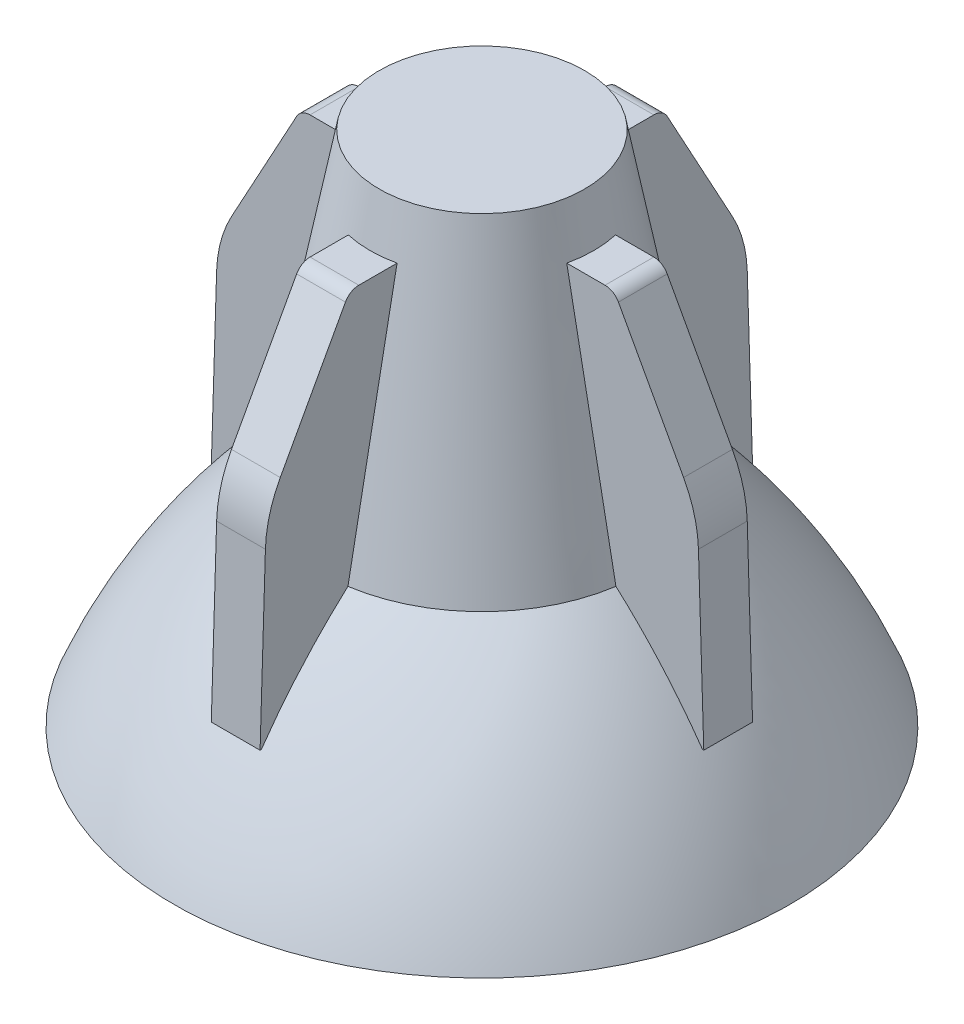
SolidWorks part; units mm, degrees
ref_plane "Front Plane" through (0, 0, 0) normal (0, 0, 1) x (1, 0, 0)
ref_plane "Top Plane" through (0, 0, 0) normal (0, 1, 0) x (1, 0, 0)
ref_plane "Right Plane" through (0, 0, 0) normal (1, 0, 0) x (0, 0, -1)
sketch "Sketch1" plane through (0, 0, 0) normal (0, 0, 1) x (1, 0, 0)
  line L0 (433.5511, 624.0548) -> (524.1181, 578.0747)
  line L1 (533.0823, 575.4497) -> (710.8345, 557.6264)
  line L2 (710.8345, 547.4101) -> (526.2364, 547.4101)
  line L3 (526.2364, 547.4101) -> (431.0532, 619.1347)
  arc A0 (524.1181, 578.0747) -> (533.0823, 575.4497) centre (535.6165, 600.723) ccw
  arc A1 (710.8345, 547.4101) -> (710.8345, 557.6264) centre (710.8345, 552.5182) ccw
  arc A2 (433.5511, 624.0548) -> (431.0532, 619.1347) centre (432.3022, 621.5948) ccw
  dimension "D1" = 25.4
extrude "Extrude1" [suppressed] add sketch "Sketch1" against normal blind 177.8
ref_plane "Plane1" [suppressed] through (62.433, 622.6422, 0) normal (0.0998, 0.995, 0) x (-0.995, 0.0998, 0)
sketch "Sketch5" [suppressed] plane through (62.433, 622.6422, 0) normal (0.0998, 0.995, 0) x (-0.995, 0.0998, 0)
  line L0 (-627.8735, 0) -> (-668.1454, 0)
  line L2 (-473.0095, -177.8) -> (-473.0095, 0) construction
  line L3 (-651.653, 0) -> (-473.0095, 0) construction
  line L4 (-668.1454, 0) -> (-668.1454, -177.8)
  line L5 (-627.8735, -177.8) -> (-668.1454, -177.8)
  arc A0 (-627.8735, 0) -> (-627.8735, -177.8) centre (-473.0095, -88.9) ccw
extrude "Extrude5" [suppressed] cut sketch "Sketch5" against normal blind 44.45
sketch "Sketch3" plane through (0, 0, 0) normal (0, 0, 1) x (1, 0, 0)
  line L1 (527.8458, 345.2208) -> (519.3827, 353.684)
  line L2 (515.7761, 360.9723) -> (513.9637, 374.4562)
  line L3 (513.9637, 374.4562) -> (481.7195, 374.4562)
  line L5 (481.7195, 374.4562) -> (481.7195, 214.6445) construction
  line L6 (481.7195, 374.4562) -> (481.7195, 214.6445)
  line L8 (493.1619, 214.6445) -> (481.7195, 214.6445)
  arc A0 (533.1426, 335.0209) -> (527.8458, 345.2208) centre (514.3754, 331.7504) ccw
  arc A1 (519.3827, 353.684) -> (515.7761, 360.9723) centre (528.3629, 362.6642) cw
  arc A2 (493.1619, 214.6445) -> (522.6349, 234.5876) centre (493.1619, 246.3945) ccw
  arc A6 (533.1426, 335.0209) -> (522.6349, 234.5876) centre (351.114, 303.299) cw
  dimension "D1" = 19.05
  dimension "D2" = 12.7
  dimension "D3" = 31.75
revolve "Revolve2" [suppressed] add sketch "Sketch3" angle 360 about L5
ref_plane "Plane3" [suppressed] through (0, 0, 6.35) normal (0, 0, 1) x (1, 0, 0)
sketch "Sketch9" plane through (0, 0, 0) normal (0, 0, 1) x (1, 0, 0)
  line L0 (161.1424, 194.2924) -> (182.5331, 194.2924)
  line L1 (182.5331, 194.2924) -> (194.5119, 130.9759)
  line L3 (225.3348, 86.698) -> (161.1424, 86.698)
  line L5 (161.1424, 86.698) -> (161.1424, 194.2924)
  arc A0 (225.3348, 86.698) -> (194.5119, 130.9759) centre (113.0248, 41.3834) ccw
revolve "Revolve3" add sketch "Sketch9" angle 360 about L5 region at (182.1272, 129.8955, 0)
sketch "Sketch10" plane through (0, 0, 0) normal (0, 0, 1) x (1, 0, 0)
  line L0 (161.1424, 110.5751) -> (161.1424, 184.1604)
  line L1 (194.6456, 182.5072) -> (208.2162, 157.6585)
  line L4 (211.3117, 146.2725) -> (212.4203, 110.5751)
  line L5 (212.4203, 110.5751) -> (161.1424, 110.5751)
  line L6 (191.8591, 184.1604) -> (161.1424, 184.1604)
  arc A0 (225.3348, 86.698) -> (194.5119, 130.9759) centre (113.0248, 41.3834) ccw construction
  arc A1 (211.3117, 146.2725) -> (208.2162, 157.6585) centre (185.9239, 145.4841) ccw
  arc A2 (191.8591, 184.1604) -> (194.6456, 182.5072) centre (191.8591, 180.9854) cw
  dimension "D1" = 25.4
  dimension "D2" = 3.175
extrude "Extrude7" add sketch "Sketch10" along normal mid plane 10.16
ref_axis "Axis1" through (161.1424, 130.9759, 0) along (0, 1, 0)
pattern_circular "CirPattern1" count 4 over 360 about axis through (161.1424, 130.9759, 0) along (0, 1, 0) of "Extrude7"
